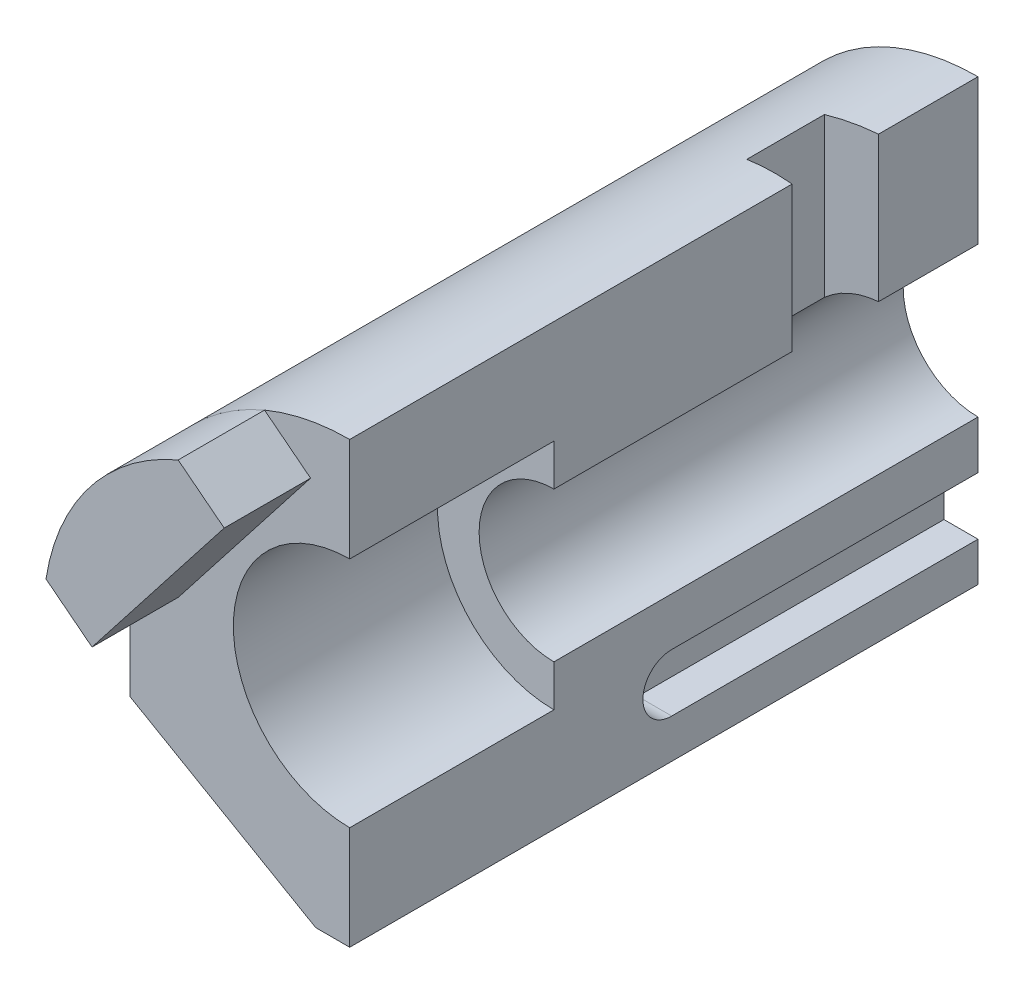
SolidWorks part; units mm, degrees
note: The reader was unsure of these and kept them because the rebuilt part matched: shared geometry of "Sketch1<4>", "Sketch1<5>".
material "1060 Alloy"
ref_plane "Front Plane" through (0, 0, 0) normal (0, 0, 1) x (1, 0, 0)
ref_plane "Top Plane" through (0, 0, 0) normal (0, 1, 0) x (1, 0, 0)
ref_plane "Right Plane" through (0, 0, 0) normal (1, 0, 0) x (0, 0, -1)
sketch "Sketch1" plane through (0, 0, 0) normal (0, 0, 1) x (1, 0, 0)
  line L0 (0, 0) -> (-13, 0)
  line L1 (-13, 0) -> (-84, 40.9919)
  line L2 (-84, 40.9919) -> (-84, 84)
  line L3 (0, 168) -> (0, 112.575)
  line L4 (0, 55.425) -> (0, 0)
  line L5 (-32.5304, 161.4453) -> (-14.9464, 147.7072)
  line L6 (-14.9464, 147.7072) -> (-65.4307, 83.0903)
  line L7 (-65.4307, 83.0903) -> (-83.0146, 96.8284)
  line L8 (-40.1885, 115.3987) -> (0, 84) construction
  arc A0 (-84, 84) -> (0, 168) centre (0, 84) cw
  arc A1 (0, 112.575) -> (0, 55.425) centre (0, 84) ccw
  arc A2 (0, 128.45) -> (0, 39.55) centre (0, 84) ccw
  point P13 (0, 27.7125)
  point P14 (-42.2228, 108.7675)
  point P16 (-6.5, 0)
  dimension "D8" = 88.9
  dimension "D9" = 57.15
  dimension "D1" = 13
  dimension "D2" = 84
  dimension "D3" = 30
  dimension "D4" = 84
  dimension "D5" = 51
  dimension "D6" = 82
  dimension "D7" = 38
extrude "Boss-Extrude1" add sketch "Sketch1" along normal blind 33 contours A0 L7 L6 L5
extrude "Boss-Extrude2" add sketch "Sketch1<4>" against normal blind 240 separate body contours L8 L6 L7 A0 L2 L1 L0 L4 A2 | L6 L8 A2 L3 A0 L5 | A0 L7 L6 L5
sketch "Sketch1<4>" plane through (0, 0, 0) normal (0, 0, 1) x (1, 0, 0) same geometry as "Sketch1"
extrude "Boss-Extrude3" add sketch "Sketch1<5>" against normal up to surface (162 mm away) from offset 78 contours A2 L8 A1 L3 | L8 A2 L4 A1 up to face at (-34.6924, 68.3413, -240) offset against normal yes
sketch "Sketch1<5>" plane through (0, 0, 0) normal (0, 0, 1) x (1, 0, 0) same geometry as "Sketch1"
sketch "Sketch2" plane through (0, 0, 0) normal (1, 0, 0) x (0, 0, -1)
  line L0 (240, 37) -> (123, 37)
  line L1 (240, 55.425) -> (240, 0) construction
  line L2 (123, 15) -> (240, 15)
  line L3 (240, 15) -> (240, 37)
  line L4 (240, 0) -> (0, 0) construction
  arc A0 (123, 37) -> (123, 15) centre (123, 26) ccw
  point P9 (240, 26)
  dimension "D2" = 11
  dimension "D1" = 26
  dimension "D3" = 117
extrude "Cut-Extrude1" cut sketch "Sketch2" against normal blind 13
ref_plane "Plane1" through (0, 168, 0) normal (0, 1, 0) x (1, 0, 0)
sketch "Sketch3" plane through (0, 168, 0) normal (0, 1, 0) x (1, 0, 0)
  line L0 (0, 169) -> (-19, 170.6623)
  line L1 (0, 240) -> (0, 0) construction
  line L2 (-19, 170.6623) -> (-19, 200.3377)
  line L3 (-19, 200.3377) -> (0, 202)
  line L4 (0, 202) -> (0, 169)
  dimension "D3" = 19
  dimension "D2" = 33
  dimension "D1" = 38
  dimension "D4" = 85
  dimension "D5" = 85
extrude "Cut-Extrude2" cut sketch "Sketch3" against normal up to next
equation "\"A\" = 240"
equation "\"B\" = 117"
equation "\"C\" = 84"
equation "\"D2@Sketch1\"=\"C\""
equation "\"D4@Sketch1\"=\"C\""
equation "\"D1@Boss-Extrude2\"=\"A\""
equation "\"D3@Sketch2\"=\"B\""
equation "\"D\"= 5"
equation "\"D4@Sketch3\"=90-\"D\""
equation "\"D5@Sketch3\"=90-\"D\""
